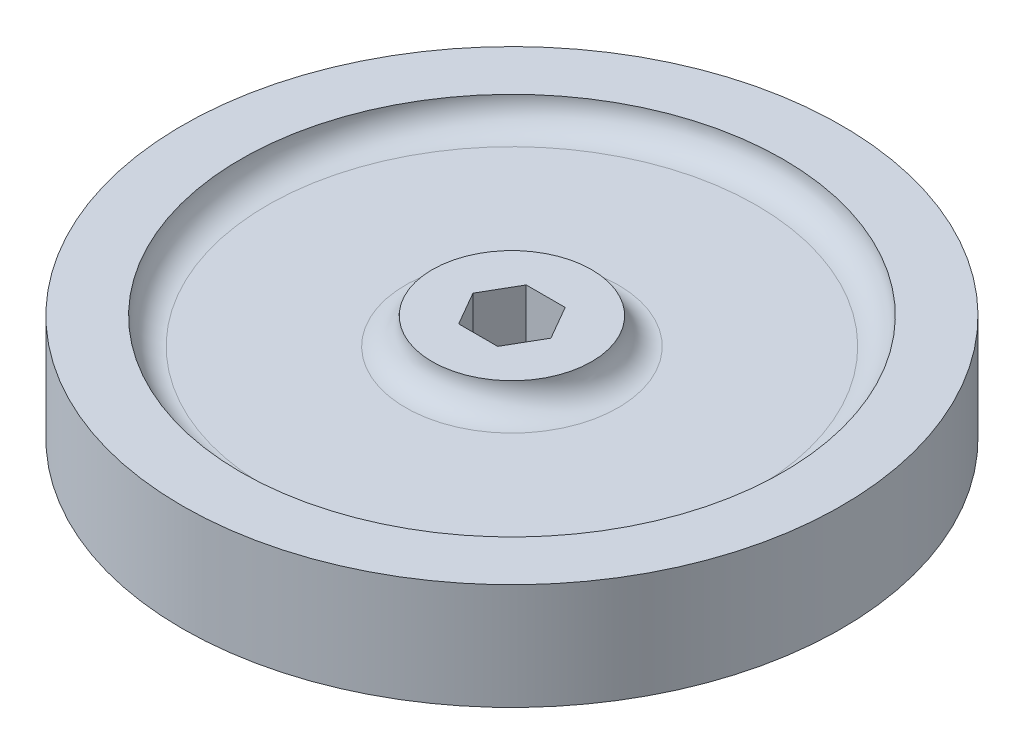
SolidWorks part; units mm, degrees
ref_plane "Plan de face" through (0, 0, 0) normal (0, 0, 1) x (1, 0, 0)
ref_plane "Plan de dessus" through (0, 0, 0) normal (0, 1, 0) x (1, 0, 0)
ref_plane "Plan de droite" through (0, 0, 0) normal (1, 0, 0) x (0, 0, -1)
sketch "Esquisse1" plane through (0, 0, 0) normal (0, 1, 0) x (1, 0, 0)
  line L1 (-7.3323, 0) -> (-3.6662, -6.35)
  line L2 (-3.6662, -6.35) -> (3.6662, -6.35)
  line L3 (3.6662, -6.35) -> (7.3323, 0)
  line L4 (7.3323, 0) -> (3.6662, 6.35)
  line L5 (3.6662, 6.35) -> (-3.6662, 6.35)
  line L6 (-3.6662, 6.35) -> (-7.3323, 0)
  circle A0 centre (0, 0) radius 6.35 construction
  circle A1 centre (0, 0) radius 15
  circle A2 centre (0, 0) radius 55
  circle A3 centre (0, 0) radius 62
  circle A4 centre (0, 0) radius 51
  dimension "D2" = 30
  dimension "D3" = 110
  dimension "D4" = 124
  dimension "D5" = 102
  dimension "D1" = 12.7
extrude "Boss.-Extru.1" add sketch "Esquisse1" along normal blind 10 contours A2 | L2 L3 L4 L5 L6 L1
extrude "Enlèv. mat.-Extru.1" cut sketch "Esquisse1<11>" along normal blind 5 contours A4 | A1
sketch "Esquisse1<11>" plane through (0, 0, 0) normal (0, 1, 0) x (1, 0, 0) same geometry as "Esquisse1"
fillet "Congé1" radius 5 2 edges at (0, 5, 15) (0, 5, 51)
mirror "Symétrie1" about plane through (0, 10, 0) normal (0, 1, 0) of "Congé1", "Enlèv. mat.-Extru.1", "Boss.-Extru.1"
extrude "Boss.-Extru.4" add sketch "Esquisse1<14>" along normal blind 20 contours A2 | A3
sketch "Esquisse1<14>" plane through (0, 0, 0) normal (0, 1, 0) x (1, 0, 0) same geometry as "Esquisse1"
